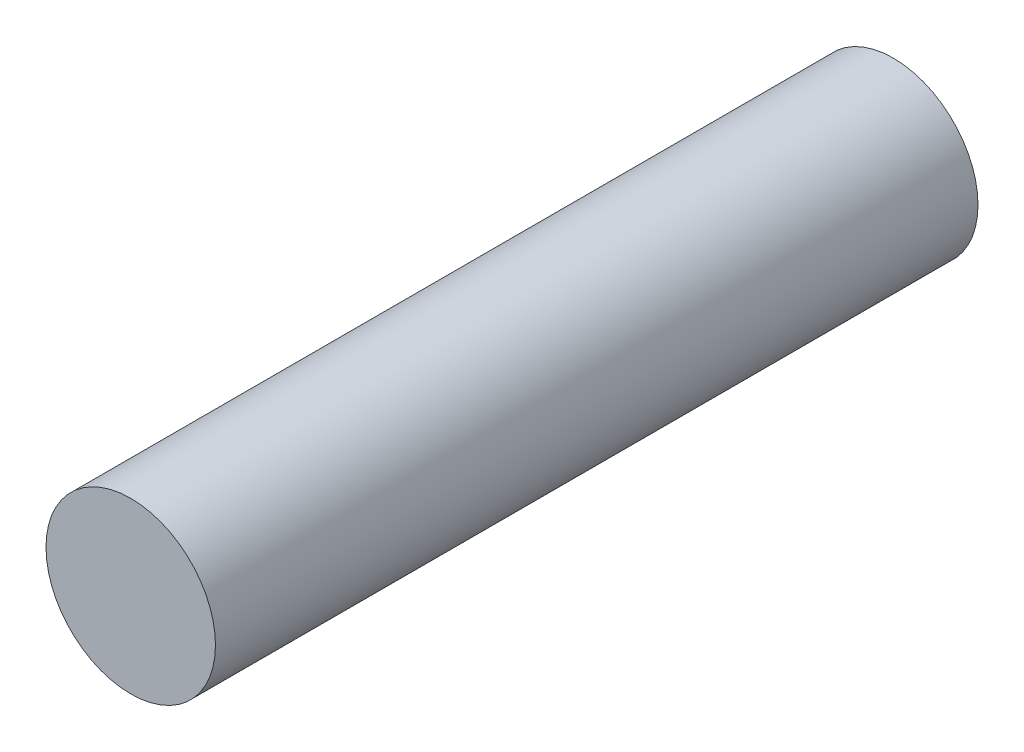
SolidWorks part; units mm, degrees
ref_plane "Front Plane" through (0, 0, 0) normal (0, 0, 1) x (1, 0, 0)
ref_plane "Top Plane" through (0, 0, 0) normal (0, 1, 0) x (1, 0, 0)
ref_plane "Right Plane" through (0, 0, 0) normal (1, 0, 0) x (0, 0, -1)
sketch "Sketch1" plane through (0, 0, 0) normal (0, 0, 1) x (1, 0, 0)
  circle A0 centre (0, 0) radius 1
extrude "Boss-Extrude1" add sketch "Sketch1" along normal blind 9
